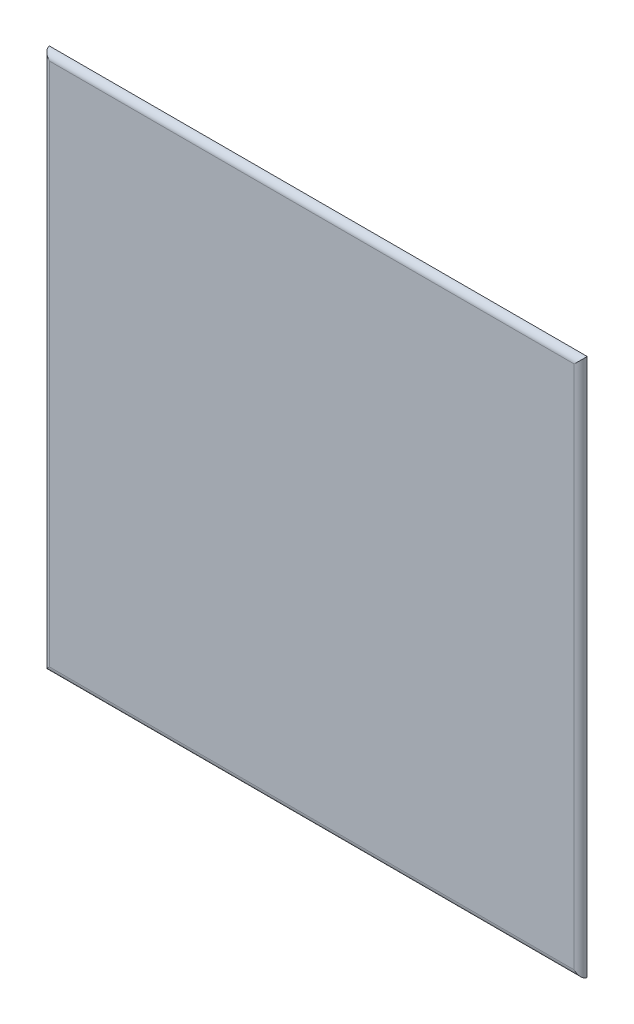
SolidWorks part; units mm, degrees
ref_plane "前视基准面" through (0, 0, 0) normal (0, 0, 1) x (1, 0, 0)
ref_plane "上视基准面" through (0, 0, 0) normal (0, 1, 0) x (1, 0, 0)
ref_plane "右视基准面" through (0, 0, 0) normal (1, 0, 0) x (0, 0, -1)
other "Configuration Table"
sketch "草图1" plane through (0, 0, 0) normal (0, 0, 1) x (1, 0, 0)
  line L1 (-74.75, -74.75) -> (74.75, -74.75)
  line L2 (-74.75, -74.75) -> (-74.75, 74.75)
  line L3 (-74.75, 74.75) -> (74.75, 74.75)
  line L4 (74.75, -74.75) -> (74.75, 74.75)
  line L5 (-74.75, -74.75) -> (74.75, 74.75) construction
  line L6 (-74.75, 74.75) -> (74.75, -74.75) construction
  point P0 (0, 0)
  dimension "D1" = 149.5
  dimension "D2" = 149.5
extrude "凸台-拉伸1" add sketch "草图1" along normal blind 3
sketch "草图2" plane through (0, 0, 3) normal (0, 0, 1) x (1, 0, 0)
  line L1 (-82.5, 82.5) -> (82.5, 82.5)
  line L2 (-82.5, 82.5) -> (-82.5, -82.5)
  line L3 (-82.5, -82.5) -> (82.5, -82.5)
  line L4 (82.5, 82.5) -> (82.5, -82.5)
  line L5 (-82.5, 82.5) -> (82.5, -82.5) construction
  line L6 (-82.5, -82.5) -> (82.5, 82.5) construction
  point P0 (0, 0)
  dimension "D1" = 165
extrude "凸台-拉伸2" add sketch "草图2" along normal blind 2
fillet "圆角1" radius 1 4 edges at (74.75, 74.75, 1.5) (-74.75, 74.75, 1.5) (-74.75, -74.75, 1.5) (74.75, -74.75, 1.5)
fillet "圆角2" radius 2 4 edges at (0, -82.5, 5) (-82.5, 0, 5) (0, 82.5, 5) (82.5, 0, 5)
